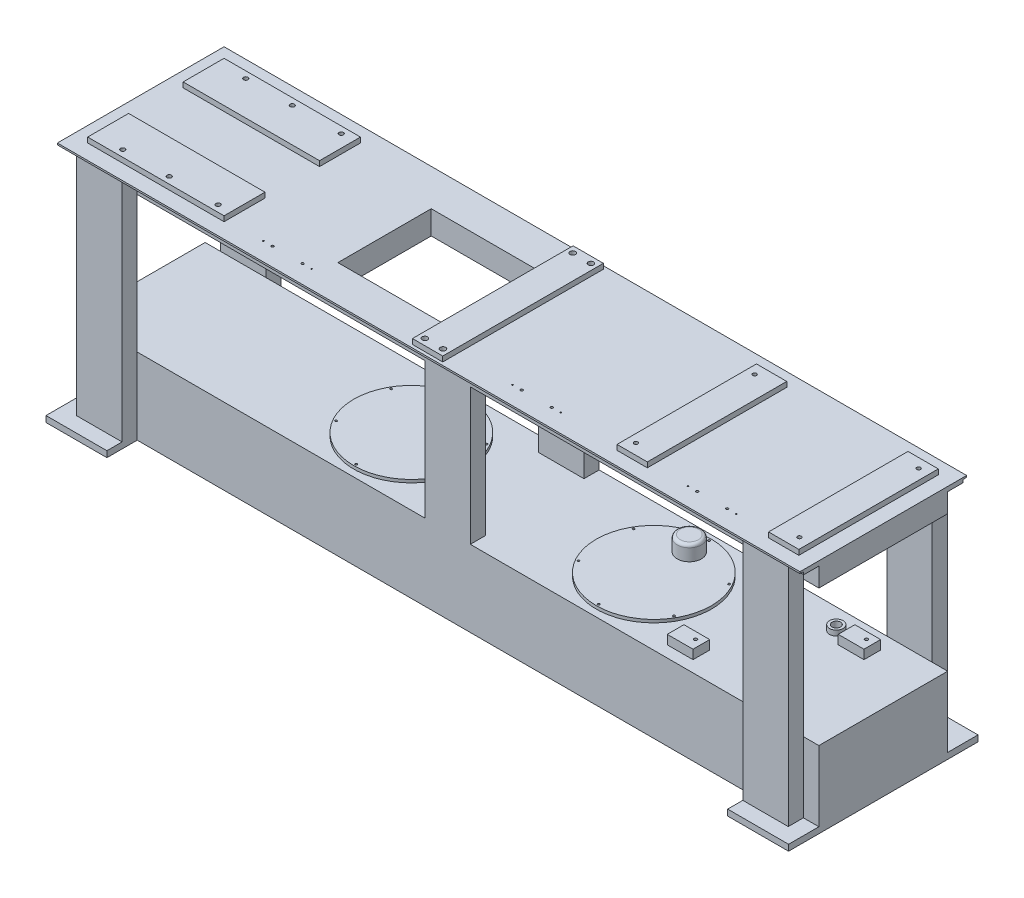
SolidWorks part; units mm, degrees
ref_plane "Front Plane" through (0, 0, 0) normal (0, 0, 1) x (1, 0, 0)
ref_plane "Top Plane" through (0, 0, 0) normal (0, 1, 0) x (1, 0, 0)
ref_plane "Right Plane" through (0, 0, 0) normal (1, 0, 0) x (0, 0, -1)
sketch "Sketch1" plane through (0, 0, 0) normal (0, 0, 1) x (1, 0, 0)
  line L1 (-1225, -390) -> (1225, -390)
  line L2 (-1225, -390) -> (-1225, 390)
  line L3 (-1225, 390) -> (1225, 390)
  line L4 (1225, -390) -> (1225, 390)
  line L5 (-1225, -390) -> (1225, 390) construction
  line L6 (-1225, 390) -> (1225, -390) construction
  point P0 (0, 0)
  dimension "D1" = 2450
  dimension "D2" = 780
extrude "Corpo" add sketch "Sketch1" against normal blind 625
sketch "Sketch3" plane through (0, 0, 0) normal (0, 0, 1) x (1, 0, 0)
  line L0 (1225, -390) -> (1225, 390) construction
  line L1 (1225, 384.4) -> (-1225, 384.4)
  line L2 (1225, 384.4) -> (1225, -370)
  line L3 (1225, -370) -> (-1225, -370)
  line L4 (-1225, 384.4) -> (-1225, -370)
  line L5 (-1225, -390) -> (1225, -390) construction
  line L6 (1225, 390) -> (-1225, 390) construction
  dimension "D1" = 20
  dimension "D2" = 5.6
  dimension "D3" = 2450
extrude "Corte dos Pés" cut sketch "Sketch3" against normal blind 50
ref_plane "Plano de Referência" through (0, 0, -312.5) normal (0, 0, 1) x (1, 0, 0)
mirror "Espelhamento - Corte dos Pés" about plane through (0, 0, -312.5) normal (0, 0, 1) of "Corte dos Pés"
sketch "Sketch4" plane through (1225, 0, 0) normal (1, 0, 0) x (0, 0, -1)
  line L0 (50, -370) -> (0, -370) construction
  line L1 (0, 375) -> (100, 375)
  line L2 (0, 375) -> (0, -370)
  line L3 (0, -370) -> (100, -370)
  line L4 (100, 375) -> (100, -370)
  line L6 (625, 390) -> (0, 390) construction
  dimension "D1" = 100
  dimension "D2" = 15
extrude "Corte Lateral" cut sketch "Sketch4" against normal blind 51
mirror "Espelhamento - Corte Lateral 1" about plane through (0, 0, -312.5) normal (0, 0, 1) of "Corte Lateral"
mirror "Espelhamento - Corte Lateral 2" about plane through (0, 0, 0) normal (1, 0, 0) of "Corte Lateral", "Espelhamento - Corte Lateral 1"
sketch "Sketch5" plane through (1225, 0, 0) normal (1, 0, 0) x (0, 0, -1)
  line L0 (312.5, 390) -> (312.5, -390) construction
  line L1 (625, 390) -> (0, 390) construction
  line L2 (625, -390) -> (0, -390) construction
  line L3 (0, -390) -> (0, -370) construction
  line L4 (100, -138) -> (525, -138)
  line L5 (100, -138) -> (100, 312)
  line L6 (100, 312) -> (525, 312)
  line L7 (525, -138) -> (525, 312)
  line L8 (100, -138) -> (525, 312) construction
  line L9 (100, 312) -> (525, -138) construction
  point P6 (312.5, 87)
  dimension "D1" = 252
  dimension "D2" = 100
  dimension "D3" = 450
extrude "Corte Interno" cut sketch "Sketch5" against normal through all
sketch "Sketch6" plane through (0, 0, -50) normal (0, 0, 1) x (1, 0, 0)
  line L0 (1225, 384.4) -> (-1225, 384.4) construction
  line L1 (1024, 384.4) -> (1174, 384.4)
  line L2 (1024, 384.4) -> (1024, -370)
  line L3 (1024, -370) -> (1174, -370)
  line L4 (1174, 384.4) -> (1174, -370)
  line L5 (-1174, -370) -> (1174, -370) construction
  line L6 (1174, 375) -> (1174, -370) construction
  line L7 (0, 384.4) -> (0, -370)
  line L8 (-1024, -370) -> (-1174, -370)
  line L9 (-1174, 384.4) -> (-1174, -370)
  line L10 (-1024, 384.4) -> (-1174, 384.4)
  line L11 (-1024, 384.4) -> (-1024, -370)
  line L13 (-1024, 384.4) -> (1024, 384.4)
  line L14 (-1024, 384.4) -> (-1024, -370)
  line L15 (-1024, -370) -> (1024, -370)
  line L16 (1024, 384.4) -> (1024, -370)
  line M16 (-1174, -370) -> (1174, -370)
  line M20 (1225, 384.4) -> (-1225, 384.4)
  dimension "D1" = 150
extrude "Corte das Pernas" cut sketch "Sketch6" against normal blind 50 contours L11 L7 M20 M16 | L7 L2 M20 M16 region at (512, 7.2, -50) region at (-512, 7.2, -50)
mirror "Espelhamento - Corte das Pernas" about plane through (0, 0, -312.5) normal (0, 0, 1) of "Corte das Pernas"
sketch "Sketch7" plane through (0, 0, -100) normal (0, 0, 1) x (1, 0, 0)
  line L0 (0, 312) -> (0, -138) construction
  line L1 (-1024, 312) -> (1024, 312) construction
  line L2 (1024, -138) -> (-1024, -138) construction
  line L4 (-75, -138) -> (75, -138)
  line L5 (-75, -138) -> (-75, 312)
  line L6 (-75, 312) -> (75, 312)
  line L7 (75, -138) -> (75, 312)
  line L8 (-75, -138) -> (75, 312) construction
  line L9 (-75, 312) -> (75, -138) construction
  point P6 (0, 87)
  dimension "D1" = 150
extrude "Coluna Central" add sketch "Sketch7" against normal blind 50
mirror "Espelhamento - Coluna Central" about plane through (0, 0, -312.5) normal (0, 0, 1) of "Coluna Central"
sketch "Sketch8" plane through (0, 390, 0) normal (0, 1, 0) x (1, 0, 0)
  line L0 (1126.5, 542.5) -> (1126.5, 82.5) construction
  line L2 (1076.5, 82.5) -> (1176.5, 82.5)
  line L3 (1076.5, 82.5) -> (1076.5, 542.5)
  line L4 (1076.5, 542.5) -> (1176.5, 542.5)
  line L5 (1176.5, 82.5) -> (1176.5, 542.5)
  line L6 (1076.5, 82.5) -> (1176.5, 542.5) construction
  line L7 (1076.5, 542.5) -> (1176.5, 82.5) construction
  line L9 (1225, 625) -> (1225, 0) construction
  line L10 (1225, 312.5) -> (1126.5, 312.5) construction
  line L21 (576.5, 82.5) -> (576.5, 542.5)
  line L22 (576.5, 82.5) -> (676.5, 82.5)
  line L23 (676.5, 82.5) -> (676.5, 542.5)
  line L24 (576.5, 542.5) -> (676.5, 542.5)
  line L25 (36.5, 312.5) -> (576.5, 312.5) construction
  line L26 (-63.5, 577.5) -> (36.5, 577.5)
  line L27 (-63.5, 577.5) -> (-63.5, 47.5)
  line L28 (-63.5, 47.5) -> (36.5, 47.5)
  line L29 (36.5, 577.5) -> (36.5, 47.5)
  line L30 (-63.5, 312.5) -> (-1225, 312.5) construction
  line L31 (-1175, 537.5) -> (-725, 537.5)
  line L32 (-1175, 537.5) -> (-1175, 402.5)
  line L33 (-1175, 402.5) -> (-725, 402.5)
  line L34 (-725, 537.5) -> (-725, 402.5)
  line L35 (-1225, 625) -> (-1225, 0) construction
  line L40 (-1175, 222.5) -> (-725, 222.5)
  line L41 (-725, 87.5) -> (-725, 222.5)
  line L42 (-1175, 87.5) -> (-725, 87.5)
  line L43 (-1175, 87.5) -> (-1175, 222.5)
  point P2 (1126.5, 312.5)
  dimension "D1" = 48.5
  dimension "D2" = 100
  dimension "D3" = 460
  dimension "D4" = 2
  dimension "D5" = 600
  dimension "D6" = 100
  dimension "D7" = 530
  dimension "D8" = 740
  dimension "D9" = 135
  dimension "D10" = 450
  dimension "D12" = 50
  dimension "D11" = 225
extrude "Resaltos da Mesa" add sketch "Sketch8" along normal blind 17
sketch "Sketch9" plane through (0, 390, 0) normal (0, 1, 0) x (1, 0, 0)
  line L0 (-247, 312.5) -> (-1225, 312.5) construction
  line L1 (-420.5, 158.5) -> (-73.5, 158.5)
  line L2 (-420.5, 158.5) -> (-420.5, 466.5)
  line L3 (-420.5, 466.5) -> (-73.5, 466.5)
  line L4 (-73.5, 158.5) -> (-73.5, 466.5)
  line L5 (-420.5, 158.5) -> (-73.5, 466.5) construction
  line L6 (-420.5, 466.5) -> (-73.5, 158.5) construction
  line L7 (-1225, 625) -> (-1225, 0) construction
  line L8 (-63.5, 577.5) -> (-63.5, 47.5) construction
  point P0 (-247, 312.5)
  dimension "D1" = 308
  dimension "D2" = 347
  dimension "D3" = 10
extrude "Rasgo 347x308" cut sketch "Sketch9" against normal up to next
sketch "Sketch16" plane through (0, 390, 0) normal (0, 1, 0) x (1, 0, 0)
  line L0 (-1225, 587.5) -> (1225, 587.5)
  line L1 (-1225, 0) -> (1225, 0)
  line L2 (-1225, 0) -> (-1225, 625)
  line L3 (-1225, 625) -> (1225, 625)
  line L4 (1225, 0) -> (1225, 625)
  line L5 (-1225, 37.5) -> (1225, 37.5)
  line M22 (-1225, 0) -> (1225, 0)
  line M23 (1225, 0) -> (1225, 625)
  line M24 (1225, 625) -> (-1225, 625)
  line M25 (-1225, 625) -> (-1225, 0)
  dimension "D1" = 37.5
  dimension "D2" = 37.5
extrude "Ajuste - Tamanho da Mesa" cut sketch "Sketch16" against normal up to next contours L5 L2 M22 M23 | L0 M25 M23 M24 region at (0, 390, -606.25) region at (0, 390, -18.75)
sketch "Sketch18" plane through (0, 0, -525) normal (0, 0, -1) x (-1, 0, 0)
  line L0 (1024, 384.4) -> (1024, 312) construction
  line L1 (-1024, 384.4) -> (1024, 384.4)
  line L2 (-1024, 384.4) -> (-1024, 375)
  line L3 (-1024, 375) -> (1024, 375)
  line L4 (1024, 384.4) -> (1024, 375)
  line L5 (1225, 390) -> (-1225, 390) construction
  dimension "D1" = 15
extrude "Rebaixo da Mesa - Lado 1" add sketch "Sketch18" along normal up to surface (50 mm away) up to face at (1141, 129.8, -575)
sketch "Sketch38" plane through (0, 0, -100) normal (0, 0, 1) x (1, 0, 0)
  line L0 (1024, 384.4) -> (1024, 312) construction
  line L1 (-1024, 384.4) -> (1024, 384.4)
  line L2 (-1024, 384.4) -> (-1024, 375)
  line L3 (-1024, 375) -> (1024, 375)
  line L4 (1024, 384.4) -> (1024, 375)
  line L5 (-1225, 390) -> (1225, 390) construction
  dimension "D1" = 15
extrude "Rebaixo da Mesa - Lado 2" add sketch "Sketch38" along normal up to surface (50 mm away) up to face at (-1141, 129.8, -50)
sketch "Sketch11" plane through (0, 390, 0) normal (0, 1, 0) x (1, 0, 0)
  line L0 (796, 97.5) -> (826, 97.5) construction
  line L1 (826, 97.5) -> (925, 97.5) construction
  line L2 (925, 97.5) -> (955, 97.5) construction
  line L3 (1225, 587.5) -> (1225, 37.5) construction
  line L4 (1225, 0) -> (-1225, 0) construction
  line L5 (586, 0) -> (586, 97.5) construction
  line L6 (586, 97.5) -> (796, 97.5) construction
  line L7 (247, 97.5) -> (217, 97.5) construction
  line L8 (346, 97.5) -> (247, 97.5) construction
  line L9 (376, 97.5) -> (346, 97.5) construction
  line L10 (-114.5, 0) -> (-114.5, 97.5) construction
  line L11 (-114.5, 97.5) -> (217, 97.5) construction
  line L12 (-605, 97.5) -> (-575, 97.5) construction
  line L13 (-575, 97.5) -> (-476, 97.5) construction
  line L14 (-476, 97.5) -> (-446, 97.5) construction
  line L15 (-1225, 37.5) -> (1225, 37.5) construction
  circle A0 centre (826, 97.5) radius 4
  circle A1 centre (925, 97.5) radius 4
  circle A2 centre (955, 97.5) radius 2.425
  circle A3 centre (796, 97.5) radius 2.425
  circle A8 centre (376, 97.5) radius 2.425
  circle A9 centre (217, 97.5) radius 2.425
  circle A10 centre (247, 97.5) radius 4
  circle A11 centre (346, 97.5) radius 4
  circle A12 centre (-575, 97.5) radius 4
  circle A13 centre (-476, 97.5) radius 4
  circle A14 centre (-446, 97.5) radius 2.425
  circle A15 centre (-605, 97.5) radius 2.425
  dimension "D1" = 270
  dimension "D2" = 30
  dimension "D3" = 99
  dimension "D4" = 30
  dimension "D5" = 4.85
  dimension "D6" = 8
  dimension "D8" = 210
  dimension "D9" = 331.5
  dimension "D7" = 60
extrude "Furos dos Pinos - Ø8" cut sketch "Sketch11" against normal blind 30 contours A1 | A0 | A11 | A10 | A13 | A12
hole_wizard "Furos dos Contrapontos - M5" positions "Sketch12" profile "Sketch13" tap size "M5x0.8" standard "ANSI Metric" end condition up to next
sketch "Sketch12" plane through (0, 390, 0) normal (0, 1, 0) x (1, 0, 0)
  point P0 (955, 97.5)
  point P3 (796, 97.5)
  point P6 (376, 97.5)
  point P9 (217, 97.5)
  point P12 (-446, 97.5)
  point P15 (-605, 97.5)
sketch "Sketch13" plane through (955, 390, -97.5) normal (1, 0, 0) x (0, 0, 1)
  line L0 (0, 0) -> (0, 15)
  line L1 (0, 15) -> (2.1, 15)
  line L2 (2.1, 15) -> (2.1, 0)
  line L5 (2.1, 0) -> (0, 0)
  line L11 (0, -6.35) -> (0, 107.95) construction
  dimension "Thru Tap Drill Dia." = 4.2
  dimension "Thru Tap Drill Depth" = 15
cosmetic thread "Hole Thread1" parameters "D2"=5
cosmetic thread "Hole Thread2" parameters "D2"=5
cosmetic thread "Hole Thread3" parameters "D2"=5
cosmetic thread "Hole Thread4" parameters "D2"=5
cosmetic thread "Hole Thread5" parameters "D2"=5
cosmetic thread "Hole Thread6" parameters "D2"=5
sketch "Sketch17" plane through (0, -370, 0) normal (0, 1, 0) x (1, 0, 0)
  line L0 (-1225, 0) -> (1225, 0) construction
  line L1 (-1024, 100) -> (1024, 100)
  line L2 (-1024, 100) -> (-1024, 0)
  line L3 (-1024, 0) -> (1024, 0)
  line L4 (1024, 100) -> (1024, 0)
  line L5 (1024, 100) -> (1024, 50) construction
extrude "Corte do chão" cut sketch "Sketch17" against normal through all
mirror "Espelhamento - Corte do chão" about plane through (0, 0, -312.5) normal (0, 0, 1) of "Corte do chão"
sketch "Sketch19" plane through (0, 407, 0) normal (0, 1, 0) x (1, 0, 0)
  line L0 (1142.5, 511.5) -> (1142.5, 118) construction
  line L1 (1176.5, 542.5) -> (1076.5, 542.5) construction
  line L2 (1076.5, 82.5) -> (1176.5, 82.5) construction
  line L3 (1142.5, 118) -> (603.5, 118) construction
  line L4 (576.5, 542.5) -> (576.5, 82.5) construction
  line L5 (1176.5, 82.5) -> (1176.5, 542.5) construction
  line L6 (-43.55, 556.6) -> (16.35, 556.6) construction
  line L7 (603.5, 118) -> (603.5, 509.5) construction
  line L9 (676.5, 542.5) -> (576.5, 542.5) construction
  line L10 (-43.55, 68.4) -> (16.35, 68.4) construction
  line L11 (-13.6, 68.4) -> (-13.6, 556.6) construction
  line L12 (-950, 402.5) -> (-950, 222.5) construction
  line L13 (-1175, 402.5) -> (-725, 402.5) construction
  line L14 (36.5, 47.5) -> (36.5, 577.5) construction
  line L15 (-725, 222.5) -> (-1175, 222.5) construction
  line L16 (-950, 312.5) -> (-725, 312.5) construction
  line L17 (-725, 312.5) -> (-725, 402.5) construction
  line L18 (36.5, 577.5) -> (-63.5, 577.5) construction
  line L21 (-63.5, 47.5) -> (36.5, 47.5) construction
  line L22 (-1081.4, 515.5) -> (-927.9, 515.5) construction
  line L23 (-927.9, 515.5) -> (-766.4, 515.5) construction
  line L24 (-725, 537.5) -> (-1175, 537.5) construction
  line L27 (-725, 402.5) -> (-725, 537.5) construction
  line L28 (-927.9, 109.5) -> (-766.4, 109.5) construction
  line L29 (-1081.4, 109.5) -> (-927.9, 109.5) construction
  circle A0 centre (1142.5, 118) radius 7
  circle A1 centre (1142.5, 511.5) radius 7
  circle A2 centre (603.5, 118) radius 7
  circle A3 centre (603.5, 509.5) radius 7
  circle A4 centre (-43.55, 556.6) radius 8.9
  circle A5 centre (16.35, 556.6) radius 8.9
  circle A6 centre (-43.55, 68.4) radius 8.9
  circle A7 centre (16.35, 68.4) radius 8.9
  circle A8 centre (-1081.4, 515.5) radius 8
  circle A9 centre (-927.9, 515.5) radius 8
  circle A10 centre (-766.4, 515.5) radius 8
  circle A11 centre (-766.4, 109.5) radius 8
  circle A12 centre (-927.9, 109.5) radius 8
  circle A13 centre (-1081.4, 109.5) radius 8
  dimension "D1" = 31
  dimension "D2" = 35.5
  dimension "D3" = 27
  dimension "D4" = 14
  dimension "D6" = 33
  dimension "D7" = 11.25
  dimension "D8" = 77.7
  dimension "D9" = 12
  dimension "D10" = 12
  dimension "D11" = 17.8
  dimension "D12" = 14
  dimension "D13" = 33.4
  dimension "D14" = 145.5
  dimension "D15" = 145.5
  dimension "D16" = 16
  dimension "D5" = 27
extrude "Furos Passantes Centrais" cut sketch "Sketch19" against normal up to next contours A7 | A6 | A4 | A5
hole_wizard "Furos da Mesa - M14" positions "Sketch20" profile "Sketch21" tap size "M14x1.5" standard "ANSI Metric" end condition up to next
sketch "Sketch20" plane through (0, 407, 0) normal (0, 1, 0) x (1, 0, 0)
  point P0 (1142.5, 118)
  point P3 (1142.5, 511.5)
  point P6 (603.5, 509.5)
  point P9 (603.5, 118)
sketch "Sketch21" plane through (1142.5, 407, -118) normal (1, 0, 0) x (0, 0, 1)
  line L0 (0, 0) -> (0, 95)
  line L1 (0, 95) -> (6.25, 95)
  line L2 (6.25, 95) -> (6.25, 0)
  line L5 (6.25, 0) -> (0, 0)
  line L11 (0, -6.35) -> (0, 107.95) construction
  dimension "Thru Tap Drill Dia." = 12.5
  dimension "Thru Tap Drill Depth" = 95
cosmetic thread "Hole Thread7" parameters "D2"=14
cosmetic thread "Hole Thread8" parameters "D2"=14
cosmetic thread "Hole Thread9" parameters "D2"=14
cosmetic thread "Hole Thread10" parameters "D2"=14
hole_wizard "Furos da Mesa - M16" positions "Sketch22" profile "Sketch23" tap size "M16x1.5" standard "ANSI Metric" end condition up to next
sketch "Sketch22" plane through (0, 407, 0) normal (0, 1, 0) x (1, 0, 0)
  point P0 (-766.4, 515.5)
  point P3 (-927.9, 515.5)
  point P6 (-1081.4, 515.5)
  point P9 (-1081.4, 109.5)
  point P12 (-927.9, 109.5)
  point P15 (-766.4, 109.5)
sketch "Sketch23" plane through (-766.4, 407, -515.5) normal (1, 0, 0) x (0, 0, 1)
  line L0 (0, 0) -> (0, 95)
  line L1 (0, 95) -> (7.25, 95)
  line L2 (7.25, 95) -> (7.25, 0)
  line L5 (7.25, 0) -> (0, 0)
  line L11 (0, -6.35) -> (0, 107.95) construction
  dimension "Thru Tap Drill Dia." = 14.5
  dimension "Thru Tap Drill Depth" = 95
cosmetic thread "Hole Thread11" parameters "D2"=16
cosmetic thread "Hole Thread12" parameters "D2"=16
cosmetic thread "Hole Thread13" parameters "D2"=16
cosmetic thread "Hole Thread14" parameters "D2"=16
cosmetic thread "Hole Thread15" parameters "D2"=16
cosmetic thread "Hole Thread16" parameters "D2"=16
sketch "Referência dos Blocos" plane through (0, -138, 0) normal (0, 1, 0) x (1, 0, 0)
  line L1 (748, 170) -> (1030, 170) construction
  line L2 (1030, 170) -> (1030, 452) construction
  line L3 (1030, 452) -> (748, 452) construction
  line L4 (748, 452) -> (748, 170) construction
  line L6 (1225, 100) -> (1225, 525) construction
  line L7 (1024, 100) -> (75, 100) construction
  circle A0 centre (748, 170) radius 6
  circle A1 centre (1030, 170) radius 6
  circle A2 centre (748, 452) radius 6
  circle A3 centre (1030, 452) radius 6
  dimension "D3" = 12
  dimension "D1" = 282
  dimension "D2" = 282
  dimension "D4" = 195
  dimension "D5" = 70
extrude "Referência de Encaixe dos Blocos" cut sketch "Referência dos Blocos" against normal blind 10
sketch "Sketch26" plane through (0, -138, 0) normal (0, 1, 0) x (1, 0, 0)
  line L0 (1225, 100) -> (1225, 525) construction
  line L2 (75, 525) -> (1024, 525) construction
  circle A0 centre (925, 457.5) radius 22.5
  dimension "D1" = 45
  dimension "D2" = 300
  dimension "D3" = 45
extrude "Encaixe do Cano da Base" add sketch "Sketch26" along normal blind 17
hole_wizard "Furo do Cano da Base - M30" positions "Sketch27" profile "Sketch28" tap size "M30x2.0" standard "ANSI Metric"
sketch "Sketch27" plane through (0, -121, 0) normal (0, 1, 0) x (1, 0, 0)
  point P0 (925, 457.5)
cosmetic thread "Hole Thread17" parameters "D1"=269, "D2"=30
sketch "Sketch28" plane through (925, -121, -457.5) normal (1, 0, 0) x (0, 0, 1)
  line L0 (0, 0) -> (0, 38.412)
  line L1 (0, 38.412) -> (14, 30)
  line L2 (14, 30) -> (14, 0)
  line L5 (14, 0) -> (0, 0)
  line L10 (0, 38.412) -> (-14, 30) construction
  line L11 (0, -6.35) -> (0, 107.95) construction
  dimension "Tap Drill Dia." = 28
  dimension "Tap Drill Depth" = 30
  dimension "Drill Angle" = 118
sketch "Sketch29" plane through (0, -138, 0) normal (0, 1, 0) x (1, 0, 0)
  line L0 (75, 475) -> (75, 525) construction
  line L1 (1225, 312.5) -> (468, 312.5) construction
  line L2 (1225, 100) -> (1225, 525) construction
  line L3 (468, 312.5) -> (-332, 312.5) construction
  circle A0 centre (468, 312.5) radius 190
  circle A1 centre (-332, 312.5) radius 190
  dimension "D1" = 380
  dimension "D2" = 393
  dimension "D3" = 420
extrude "Ressaltos da Base" add sketch "Sketch29" along normal blind 10
sketch "Posição dos Furos dos Ressaltos" plane through (0, -128, 0) normal (0, 1, 0) x (1, 0, 0)
  line L0 (468, 312.5) -> (468, 494.5) construction
  line L2 (278, 312.5) -> (-142, 312.5) construction
  line L3 (68, 312.5) -> (68, 475) construction
  line L4 (-75, 475) -> (75, 475) construction
  circle A0 centre (468, 312.5) radius 182 construction
  circle A1 centre (468, 494.5) radius 4
  circle A2 centre (625.6166, 403.5) radius 4
  circle A3 centre (625.6166, 221.5) radius 4
  circle A4 centre (468, 130.5) radius 4
  circle A5 centre (310.3834, 221.5) radius 4
  circle A6 centre (310.3834, 403.5) radius 4
  circle A7 centre (468, 312.5) radius 190 construction
  circle A8 centre (-332, 312.5) radius 190 construction
  circle A9 centre (625.6166, 403.5) radius 4
  circle A10 centre (625.6166, 221.5) radius 4
  circle A11 centre (310.3834, 221.5) radius 4
  circle A12 centre (310.3834, 403.5) radius 4
  circle A13 centre (625.6166, 403.5) radius 4
  circle A14 centre (625.6166, 221.5) radius 4
  circle A15 centre (310.3834, 221.5) radius 4
  circle A16 centre (310.3834, 403.5) radius 4
  circle A17 centre (625.6166, 403.5) radius 4
  circle A18 centre (625.6166, 221.5) radius 4
  circle A19 centre (310.3834, 221.5) radius 4
  circle A20 centre (310.3834, 403.5) radius 4
  circle A21 centre (-332, 312.5) radius 182 construction
  circle A22 centre (-174.3834, 403.5) radius 4
  circle A23 centre (-174.3834, 221.5) radius 4
  circle A24 centre (-489.6166, 221.5) radius 4
  circle A25 centre (-489.6166, 403.5) radius 4
  circle A26 centre (-174.3834, 403.5) radius 4
  circle A27 centre (-174.3834, 221.5) radius 4
  circle A28 centre (-489.6166, 221.5) radius 4
  circle A29 centre (-489.6166, 403.5) radius 4
  circle A30 centre (-174.3834, 403.5) radius 4
  circle A31 centre (-174.3834, 221.5) radius 4
  circle A32 centre (-489.6166, 221.5) radius 4
  circle A33 centre (-489.6166, 403.5) radius 4
  circle A34 centre (-174.3834, 403.5) radius 4
  circle A35 centre (-174.3834, 221.5) radius 4
  circle A36 centre (-332, 130.5) radius 4
  circle A37 centre (-489.6166, 221.5) radius 4
  circle A38 centre (-489.6166, 403.5) radius 4
  circle A39 centre (-332, 494.5) radius 4
  point P18 (468, 312.5)
  point P66 (-332, 312.5)
  dimension "D1" = 364
  dimension "D2" = 8
  dimension "D3" = 6
hole_wizard "Furos dos Ressaltos - M8" positions "Sketch35" profile "Sketch36" tap size "M8x1.0" standard "ANSI Metric"
sketch "Sketch35" plane through (0, -128, 0) normal (0, 1, 0) x (1, 0, 0)
  point P0 (468, 494.5)
  point P3 (625.6166, 403.5)
  point P6 (625.6166, 221.5)
  point P9 (468, 130.5)
  point P12 (310.3834, 221.5)
  point P15 (310.3834, 403.5)
  point P19 (-332, 494.5)
  point P22 (-174.3834, 403.5)
  point P25 (-174.3834, 221.5)
  point P28 (-332, 130.5)
  point P31 (-489.6166, 221.5)
  point P34 (-489.6166, 403.5)
sketch "Sketch36" plane through (468, -128, -494.5) normal (1, 0, 0) x (0, 0, 1)
  line L0 (0, 0) -> (0, 32.103)
  line L1 (0, 32.103) -> (3.5, 30)
  line L2 (3.5, 30) -> (3.5, 0)
  line L5 (3.5, 0) -> (0, 0)
  line L10 (0, 32.103) -> (-3.5, 30) construction
  line L11 (0, -6.35) -> (0, 107.95) construction
  dimension "Tap Drill Dia." = 7
  dimension "Tap Drill Depth" = 30
  dimension "Drill Angle" = 118
cosmetic thread "Hole Thread18" parameters "D1"=16, "D2"=8
cosmetic thread "Hole Thread19" parameters "D1"=16, "D2"=8
cosmetic thread "Hole Thread20" parameters "D1"=16, "D2"=8
cosmetic thread "Hole Thread21" parameters "D1"=16, "D2"=8
cosmetic thread "Hole Thread22" parameters "D1"=16, "D2"=8
cosmetic thread "Hole Thread23" parameters "D1"=16, "D2"=8
cosmetic thread "Hole Thread24" parameters "D1"=16, "D2"=8
cosmetic thread "Hole Thread25" parameters "D1"=16, "D2"=8
cosmetic thread "Hole Thread26" parameters "D1"=16, "D2"=8
cosmetic thread "Hole Thread27" parameters "D1"=16, "D2"=8
cosmetic thread "Hole Thread28" parameters "D1"=16, "D2"=8
cosmetic thread "Hole Thread29" parameters "D1"=16, "D2"=8
sketch "Sketch37" plane through (0, -128, 0) normal (0, 1, 0) x (1, 0, 0)
  line L0 (468, 429.5) -> (468, 494.5) construction
  circle A0 centre (468, 429.5) radius 40
  circle A5 centre (468, 312.5) radius 190 construction
  dimension "D1" = 80
  dimension "D2" = 33
extrude "Tampa do Ressalto" add sketch "Sketch37" along normal blind 50
fillet "Arredondamento da Tampa" radius 10 1 edges at (468, -78, -389.5)
sketch "Sketch39" plane through (0, -138, 0) normal (0, 1, 0) x (1, 0, 0)
  line L1 (687, 137.75) -> (772, 137.75)
  line L2 (687, 137.75) -> (687, 192.75)
  line L3 (687, 192.75) -> (772, 192.75)
  line L4 (772, 137.75) -> (772, 192.75)
  circle A0 centre (748, 170) radius 6 construction
  dimension "D4" = 16.75
  dimension "D1" = 55
  dimension "D2" = 85
  dimension "D3" = 18
extrude "Bloco de Fixação" add sketch "Sketch39" along normal blind 30
pattern_linear "Blocos de Fixação - Padrão Linear" count 2 spacing 282 along (0, 0, -1) count 2 spacing 282 along (1, 0, 0) of "Bloco de Fixação"
hole_wizard "Furos dos Blocos de Fixação - M12" positions "Sketch40" profile "Sketch41" tap size "M12x1.5" standard "ANSI Metric" end condition up to next
sketch "Sketch40" plane through (0, -108, 0) normal (0, 1, 0) x (1, 0, 0)
  point P0 (748, 170)
  point P3 (748, 452)
  point P6 (1030, 452)
  point P9 (1030, 170)
sketch "Sketch41" plane through (748, -108, -170) normal (1, 0, 0) x (0, 0, 1)
  line L0 (0, 0) -> (0, 30)
  line L1 (0, 30) -> (5.25, 30)
  line L2 (5.25, 30) -> (5.25, 0)
  line L5 (5.25, 0) -> (0, 0)
  line L11 (0, -6.35) -> (0, 107.95) construction
  dimension "Thru Tap Drill Dia." = 10.5
  dimension "Thru Tap Drill Depth" = 30
cosmetic thread "Hole Thread30" parameters "D2"=12
cosmetic thread "Hole Thread31" parameters "D2"=12
cosmetic thread "Hole Thread32" parameters "D2"=12
cosmetic thread "Hole Thread33" parameters "D2"=12
